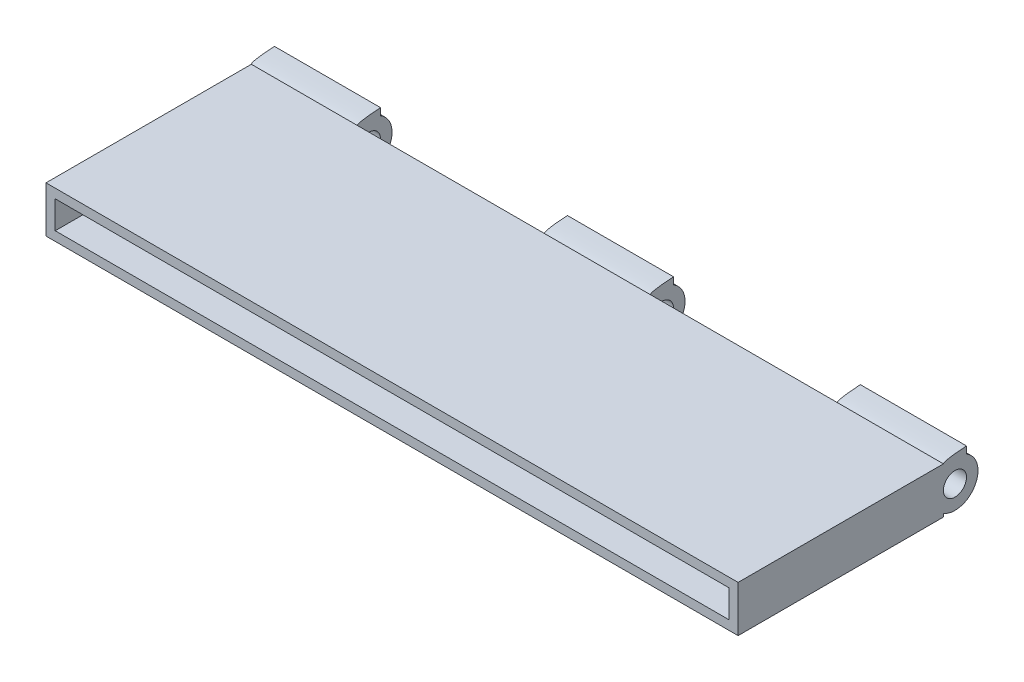
SolidWorks part; units mm, degrees
note: The reader was unsure of these and kept them because the rebuilt part matched: shared geometry of "Sketch11<2>", "Sketch11<3>".
ref_plane "Ön Düzlem" through (0, 0, 0) normal (0, 0, 1) x (1, 0, 0)
ref_plane "Üst Düzlem" through (0, 0, 0) normal (0, 1, 0) x (1, 0, 0)
ref_plane "Sağ Düzlem" through (0, 0, 0) normal (1, 0, 0) x (0, 0, -1)
sketch "Sketch1" plane through (0, 0, 0) normal (0, 0, 1) x (1, 0, 0)
  line L0 (75, 50) -> (75, -50)
  line L5 (75, -50) -> (-75, -30)
  line L6 (-75, -30) -> (-75, 30)
  line L7 (-75, 30) -> (75, 50)
  dimension "D1" = 60
  dimension "D2" = 100
  dimension "D3" = 30
  dimension "D4" = 50
  dimension "D5" = 150
  dimension "D6" = 75
extrude "Boss-Extrude1" add sketch "Sketch1" along normal blind 1
sketch "Sketch2" plane through (0, 0, 1) normal (0, 0, 1) x (1, 0, 0)
  line L0 (-75, 30) -> (-75, -30) construction
  line L1 (-75, 5) -> (139, 5)
  line L2 (-75, 5) -> (-75, -5)
  line L3 (-75, -5) -> (139, -5)
  line L4 (139, 5) -> (139, -5)
  dimension "D1" = 214
  dimension "D2" = 5
  dimension "D3" = 10
extrude "Boss-Extrude5" add sketch "Sketch2" along normal blind 100 and the other way blind 1
fillet "Fillet3" radius 15 2 edges at (0, -5, 1) (0, 5, 1) second distance 10 first distance on face at (46.3333, -5, 34) first distance on face at (46.3333, 5, 34)
sketch "Sketch6" plane through (-75, 0, 0) normal (-1, 0, 0) x (0, 0, 1)
  line L0 (9.5, 6.9868) -> (9.5, 4.3301)
  line L1 (14.5, 6.9868) -> (14.5, 4.3301)
  line L2 (14.5, -4.3301) -> (14.5, -7.2979)
  line L3 (9.5, -4.3301) -> (9.5, -7.2979)
  line L4 (9.5, 6.9868) -> (14.5, 6.9868)
  line L5 (14.5, -7.2979) -> (9.5, -7.2979)
  arc A0 (9.5, 4.3301) -> (9.5, -4.3301) centre (12, 0) ccw
  arc A1 (14.5, -4.3301) -> (14.5, 4.3301) centre (12, 0) ccw
  dimension "D1" = 10
  dimension "D2" = 12
  dimension "D3" = 5
  dimension "D4" = 2.5
extrude "Cut-Extrude2" cut sketch "Sketch6" against normal blind 229
sketch "Sketch7" plane through (0, 0, 0) normal (0, 0, -1) x (-1, 0, 0)
  line L0 (-75, 5) -> (-75, -5)
  line L1 (-75, -5) -> (-139, -5)
  line L2 (-139, -5) -> (-139, 5)
  line L3 (-139, 5) -> (-75, 5)
extrude "Cut-Extrude3" cut sketch "Sketch7" against normal blind 14
sketch "Sketch8" plane through (0, -5, 0) normal (0, -1, 0) x (-1, 0, 0)
  line L0 (83.1047, -11.7495) -> (-144.8648, -11.7495)
surface "Surface-Extrude1" sketch "Sketch8" parameters "D1"=64, "D2"=72
delete or keep bodies "Body-Delete/Keep 1" type delete bodies bodies 111
sketch "Sketch11" plane through (-75, 0, 0) normal (-1, 0, 0) x (0, 0, 1)
  circle A0 centre (12, 0) radius 5
extrude "Extrude-Thin4" add sketch "Sketch11" against normal blind 23 thin thin type one direction reverse wall 2.5
extrude "Extrude-Thin5" add sketch "Sketch11<2>" against normal blind 23 from offset 63.5 thin thin type one direction reverse wall 2.5 offset against normal yes
sketch "Sketch11<2>" plane through (-75, 0, 0) normal (-1, 0, 0) x (0, 0, 1) same geometry as "Sketch11"
extrude "Extrude-Thin6" add sketch "Sketch11<3>" against normal blind 23 from offset 127 thin thin type one direction reverse wall 2.5 offset against normal yes
sketch "Sketch11<3>" plane through (-75, 0, 0) normal (-1, 0, 0) x (0, 0, 1) same geometry as "Sketch11"
sketch "Sketch12" plane through (0, 0, 101) normal (0, 0, 1) x (1, 0, 0)
  line L14 (-73, -3) -> (137, -3)
  line L15 (137, -3) -> (137, 3)
  line L16 (137, 3) -> (-73, 3)
  line L17 (-73, 3) -> (-73, -3)
  line L18 (-75, 5) -> (-75, -5)
  line L19 (-75, -5) -> (139, -5)
  line L20 (139, -5) -> (139, 5)
  line L21 (139, 5) -> (-75, 5)
  line L22 (-75, 5) -> (-75, -5)
  line L23 (-75, -5) -> (139, -5)
  line L24 (139, -5) -> (139, 5)
  line L25 (139, 5) -> (-75, 5)
  dimension "D1" = 0
  dimension "D2" = 2
extrude "Cut-Extrude4" cut sketch "Sketch12" against normal blind 82 contours L14 L15 L16 L17
sketch "Sketch13" plane through (0, 0, 0) normal (0, 0, 1) x (1, 0, 0)
  line L0 (75, 14.8067) -> (75, -17.321)
  line L1 (75, -17.321) -> (144.1282, -17.321)
  line L2 (144.1282, -17.321) -> (144.1282, 20.1147)
  line L3 (144.1282, 20.1147) -> (75, 18.4385)
  line L4 (75, 18.4385) -> (75, 14.8067)
extrude "Cut-Extrude5" cut sketch "Sketch13" along normal blind 180
sketch "Sketch14" plane through (75, 0, 0) normal (1, 0, 0) x (0, 0, -1)
  line L0 (-101, 5) -> (-101, -5)
  line L1 (-101, -5) -> (-17.7902, -5)
  line L2 (-16, -5) -> (-101, -5) construction
  line L3 (-17.7902, -5) -> (-17.7902, 5)
  line L4 (-101, 5) -> (-16, 5) construction
  line L5 (-17.7902, 5) -> (-101, 5)
extrude "Boss-Extrude6" add sketch "Sketch14" against normal blind 2
sketch "Sketch15" plane through (75, 0, 0) normal (1, 0, 0) x (0, 0, -1)
  line L0 (-16, 5) -> (-14.3532, 5)
  line L1 (-14.3532, 5) -> (-14.3532, 5.5701)
  line L2 (-14.3532, 5.5701) -> (-16, 5.5701)
  line L3 (-16, 5.5701) -> (-16, 5)
  line L4 (-16, -5) -> (-14.3184, -5)
  line L5 (-14.3184, -5) -> (-14.3184, -5.2996)
  line L6 (-14.3184, -5.2996) -> (-16, -5.2996)
  line L7 (-16, -5.2996) -> (-16, -5)
extrude "Cut-Extrude6" cut sketch "Sketch15" against normal blind 182
sketch "Sketch16" plane through (0, -5, 0) normal (0, -1, 0) x (-1, 0, 0)
  line L0 (75, -101) -> (75, -59)
  line L1 (75, -14.5) -> (75, -101) construction
  line L2 (75, -59) -> (-75, -59)
  line L3 (-75, -14.5) -> (-75, -101) construction
  line L4 (-75, -59) -> (-75, -101)
  line L5 (-75, -101) -> (75, -101)
  dimension "D1" = 42
extrude "Cut-Extrude7" cut sketch "Sketch16" against normal blind 182
sketch "Sketch17" plane through (0, -5, 0) normal (0, -1, 0) x (1, 0, 0)
  line L0 (75, 14.5) -> (75, 9.5)
  line L1 (75, 9.5) -> (52, 9.5)
  line L2 (52, 9.5) -> (52, 14.5)
  line L3 (52, 14.5) -> (75, 14.5)
  line L4 (11.5, 9.5) -> (-11.5, 9.5)
  line L5 (-11.5, 9.5) -> (-11.5, 14.5)
  line L6 (-11.5, 14.5) -> (11.5, 14.5)
  line L7 (11.5, 14.5) -> (11.5, 9.5)
  line L8 (-52, 14.5) -> (-52, 9.5)
  line L9 (-52, 9.5) -> (-75, 9.5)
  line L12 (-75, 9.5) -> (-75, 14.5)
  line L13 (-75, 14.5) -> (-52, 14.5)
extrude "Boss-Extrude7" add sketch "Sketch17" along normal up to surface and the other way blind 1 from offset 10 up to face at (0, 0, 10.75) offset against normal yes
fillet "Fillet5" radius 10 3 edges at (-63.5, 6, 14.5) (0, 6, 14.5) (63.5, 6, 14.5) second distance 1 first distance on face at (-63.5, 6, 12) first distance on face at (0, 6, 12) first distance on face at (63.5, 6, 12)
equation "\"mm\"=1"
